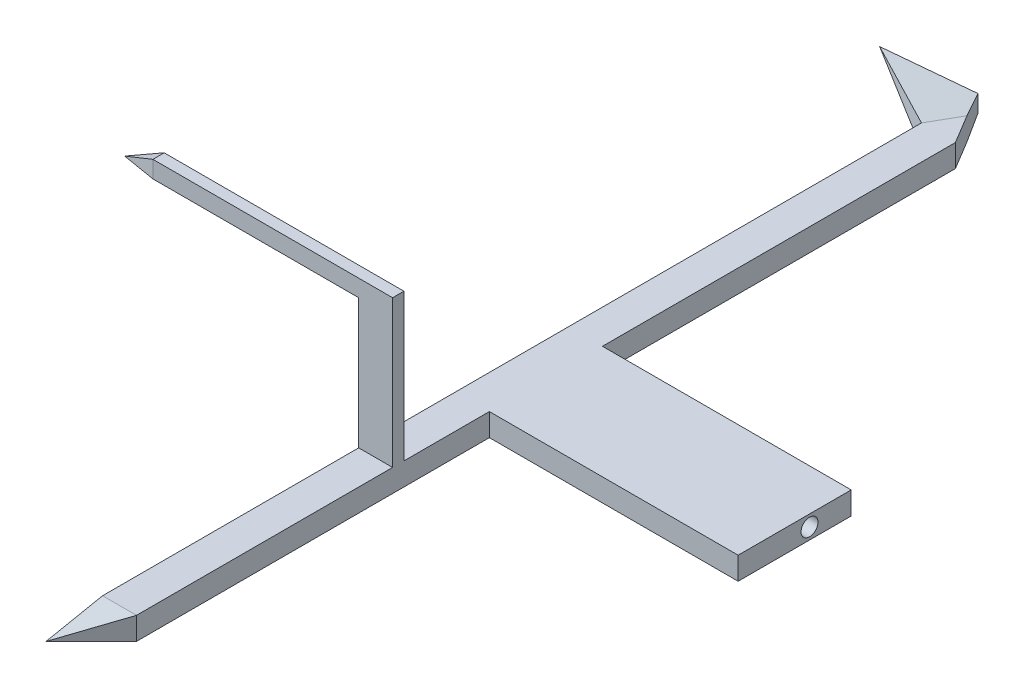
SolidWorks part; units mm, degrees
ref_plane "Front Plane" through (0, 0, 0) normal (0, 0, 1) x (1, 0, 0)
ref_plane "Top Plane" through (0, 0, 0) normal (0, 1, 0) x (1, 0, 0)
ref_plane "Right Plane" through (0, 0, 0) normal (1, 0, 0) x (0, 0, -1)
sketch "Sketch1" plane through (0, 0, 0) normal (0, 1, 0) x (1, 0, 0)
  line L0 (0, 104.6861) -> (0, -104.6861)
  line L1 (0, -104.6861) -> (7.62, -91.9861)
  line L2 (7.62, -91.9861) -> (7.62, 91.9861)
  line L3 (7.62, 91.9861) -> (0, 104.6861)
  line L4 (0, 104.6861) -> (-22.098, 104.6861)
  line L5 (-22.098, 104.6861) -> (0, 91.9861)
  line L6 (0, 91.9861) -> (0, 104.6861)
  line L7 (0, 3.3401) -> (-25.4, 3.3401)
  line L8 (7.62, 3.3401) -> (33.02, 3.3401)
  point P4 (0, 0)
  dimension "D1" = 209.3722
  dimension "D2" = 12.7
  dimension "D3" = 12.7
  dimension "D4" = 7.62
  dimension "D5" = 22.098
  dimension "D6" = 101.346
  dimension "D7" = 25.4
  dimension "D8" = 25.4
extrude "Boss-Extrude1" add sketch "Sketch1" along normal blind 5.08 contours L2 L3 L0 L1 | L4 L5 L0 region at (3.728, 0, 0) region at (-7.366, 0, -100.4528)
sketch "Sketch2" plane through (7.62, 0, 0) normal (1, 0, 0) x (0, 0, -1)
  line L0 (-91.9861, 5.08) -> (-104.6861, 2.54)
  line L1 (-104.6861, 5.08) -> (-104.6861, 0) construction
  line L2 (-104.6861, 2.54) -> (-91.9861, 0)
  line L3 (-91.9861, 0) -> (-104.6861, 0)
  line L4 (-104.6861, 0) -> (-104.6861, 2.54)
  line L5 (-104.6861, 5.08) -> (-91.9861, 5.08)
  line L6 (-104.6861, 5.08) -> (-104.6861, 2.54)
extrude "Cut-Extrude1" cut sketch "Sketch2" along normal through all both and the other way through all contours L5 L6 L0 | L4 L3 L2 region at (7.62, 0.8467, 100.4528) region at (7.62, 4.2333, 100.4528)
sketch "Sketch3" plane through (39.7397, 0, -69.1472) normal (-0.4983, 0, 0.867) x (0.867, 0, 0.4983)
  line L0 (-45.8352, 5.08) -> (-71.3227, 2.54)
  line L1 (-71.3227, 5.08) -> (-71.3227, 0) construction
  line L2 (-71.3227, 2.54) -> (-45.8352, 0)
  line L3 (-45.8352, 0) -> (-71.3227, 0)
  line L4 (-71.3227, 0) -> (-71.3227, 2.54)
  line L5 (-45.8352, 5.08) -> (-71.3227, 5.08)
  line L6 (-71.3227, 5.08) -> (-71.3227, 2.54)
  line M1 (-71.3227, 0) -> (-45.8352, 0)
  line M3 (-45.8352, 5.08) -> (-71.3227, 5.08)
  line M4 (-71.3227, 5.08) -> (-71.3227, 0)
extrude "Cut-Extrude2" cut sketch "Sketch3" against normal through all both and the other way through all contours L0 M3 M4 | L2 M4 M1 region at (-14.732, 0.8467, -100.4528) region at (-14.732, 4.2333, -100.4528)
ref_plane "Plane1" through (0, 0, 33.1724) normal (0, 0, -1) x (-1, 0, 0)
sketch "Sketch5" plane through (0, 0, 33.1724) normal (0, 0, -1) x (-1, 0, 0)
  line L0 (22.098, 2.54) -> (22.098, 34.29)
  line L1 (22.098, 34.29) -> (53.848, 34.29)
  line L2 (53.848, 34.29) -> (46.228, 38.1)
  line L3 (-7.62, 5.08) -> (-7.62, 38.1)
  line L4 (-7.62, 5.08) -> (-3.728, 5.08) construction
  line L5 (-7.62, 5.08) -> (-7.62, 0) construction
  line L6 (-7.62, 38.1) -> (46.228, 38.1)
  line L7 (0, 5.08) -> (0, 34.29)
  line L8 (0, 34.29) -> (22.098, 34.29)
  line L9 (0, 5.08) -> (-7.62, 5.08)
  dimension "D1" = 31.75
  dimension "D2" = 31.75
  dimension "D3" = 7.62
  dimension "D4" = 3.81
extrude "Boss-Extrude2" add sketch "Sketch5" along normal mid plane 2.54 contours L9 L7 L8 L1 L2 L6 L3 region at (-11.049, 34.9878, 33.1724)
sketch "Sketch6" plane through (0, 34.29, 0) normal (0, -1, 0) x (1, 0, 0)
  line L0 (-53.848, 33.1724) -> (-46.228, 34.4424)
  line L1 (-53.848, 31.9024) -> (-53.848, 34.4424) construction
  line L2 (0, 34.4424) -> (-53.848, 34.4424) construction
  line L3 (-46.228, 34.4424) -> (-53.848, 34.4424)
  line L4 (-53.848, 34.4424) -> (-53.848, 33.1724)
  line L5 (-53.848, 33.1724) -> (-53.848, 31.9024)
  line L6 (-53.848, 31.9024) -> (-46.228, 31.9024)
  line L7 (0, 31.9024) -> (-53.848, 31.9024) construction
  line L8 (-46.228, 31.9024) -> (-53.848, 33.1724)
  point P13 (0, 0)
  line M1 (0, 34.4424) -> (-53.848, 34.4424)
  line M2 (-53.848, 34.4424) -> (-53.848, 31.9024)
  line M3 (-53.848, 31.9024) -> (0, 31.9024)
  dimension "D1" = 7.62
extrude "Cut-Extrude4" cut sketch "Sketch6" against normal blind 14.732 contours L0 M2 M1 | L8 M3 M2 region at (-51.308, 34.29, 34.0191) region at (-51.308, 34.29, 32.3257)
sketch "Sketch7" plane through (0, 0, 0) normal (0, -1, 0) x (1, 0, 0)
  line L0 (7.62, 91.9861) -> (7.62, -91.9861) construction
  line L1 (7.62, 12.7) -> (63.5, 12.7)
  line L2 (7.62, 12.7) -> (7.62, -12.7)
  line L3 (7.62, -12.7) -> (63.5, -12.7)
  line L4 (63.5, 12.7) -> (63.5, -12.7)
  point P6 (63.5, 0)
  dimension "D1" = 63.5
  dimension "D2" = 25.4
extrude "Boss-Extrude3" add sketch "Sketch7" against normal up to surface (5.08 mm away) up to face at (3.7936, 5.08, -31.3392)
sketch "Sketch4" plane through (0, 0, 0) normal (-1, 0, 0) x (0, 0, 1)
  circle A0 centre (-3.3401, 2.54) radius 1.905
  dimension "D2" = 3.81
  dimension "D1" = 101.346
extrude "Cut-Extrude3" cut sketch "Sketch4" against normal through all
